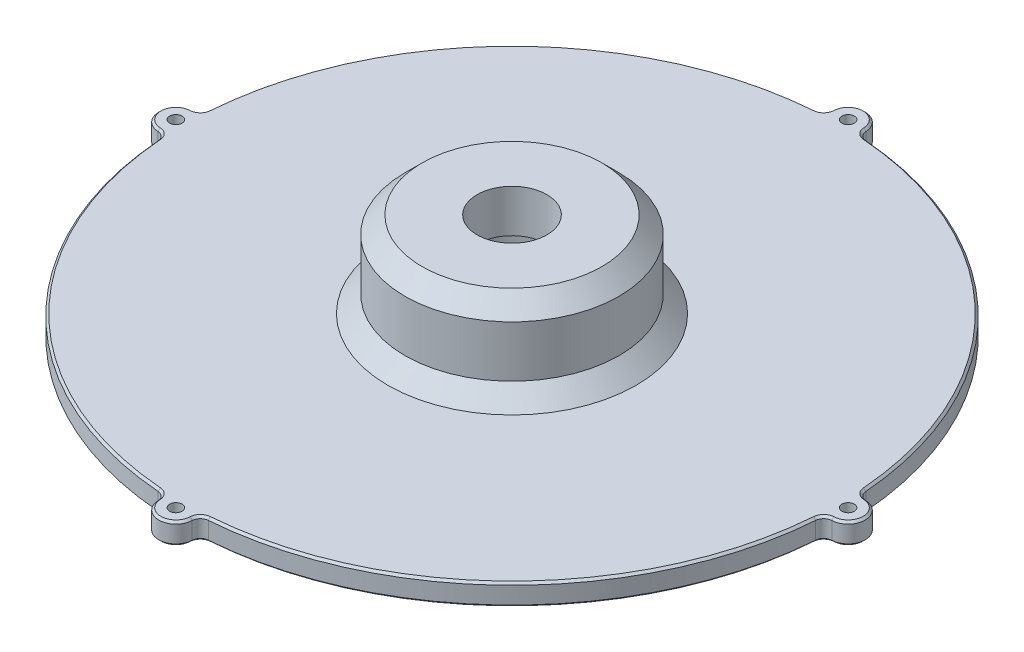
SolidWorks part; units mm, degrees
ref_plane "Płaszczyzna przednia" through (0, 0, 0) normal (0, 0, 1) x (1, 0, 0)
ref_plane "Płaszczyzna górna" through (0, 0, 0) normal (0, 1, 0) x (1, 0, 0)
ref_plane "Płaszczyzna prawa" through (0, 0, 0) normal (1, 0, 0) x (0, 0, -1)
sketch "Szkic2" plane through (0, 0, 0) normal (0, 0, 1) x (1, 0, 0)
  line L0 (15, 5) -> (15, 0)
  line L1 (15, 0) -> (77, 0)
  line L2 (77, 0) -> (77, 5)
  line L5 (77, 5) -> (15, 5)
  line L6 (0, 0) -> (0, 12.2819) construction
  line L7 (15, 5) -> (15, 15)
  line L8 (15, 15) -> (8.15, 15)
  line L9 (8.15, 15) -> (8.15, 25)
  line L10 (8.15, 25) -> (25, 25)
  line L11 (25, 25) -> (25, 5)
  dimension "D1" = 77
  dimension "D2" = 16.3
  dimension "D3" = 10
  dimension "D4" = 5
  dimension "D5" = 15
  dimension "D6" = 10
  dimension "D7" = 25
revolve "Obrót1" add sketch "Szkic2" angle 360 about L6 region at (46, 2.5, 0) region at (17.8506, 16.2756, 0)
sketch "Szkic3" plane through (0, 5, 0) normal (0, 1, 0) x (1, 0, 0)
  line L0 (0, 76) -> (0, 78.5) construction
  line L1 (-4, 76) -> (-4, 78.5)
  line L2 (4, 76) -> (4, 78.5)
  line L3 (76, 0) -> (78.5, 0) construction
  line L4 (76, 4) -> (78.5, 4)
  line L5 (76, -4) -> (78.5, -4)
  line L6 (0, -76) -> (0, -78.5) construction
  line L7 (4, -76) -> (4, -78.5)
  line L8 (-4, -76) -> (-4, -78.5)
  line L9 (-76, 0) -> (-78.5, 0) construction
  line L10 (-76, -4) -> (-78.5, -4)
  line L11 (-76, 4) -> (-78.5, 4)
  arc A1 (-4, 76) -> (4, 76) centre (0, 76) ccw
  arc A2 (4, 78.5) -> (-4, 78.5) centre (0, 78.5) ccw
  circle A3 centre (0, 78.5) radius 1.45
  circle A4 centre (78.5, 0) radius 1.45
  arc A5 (76, 4) -> (76, -4) centre (76, 0) ccw
  arc A6 (78.5, -4) -> (78.5, 4) centre (78.5, 0) ccw
  circle A7 centre (0, -78.5) radius 1.45
  arc A8 (4, -76) -> (-4, -76) centre (0, -76) ccw
  arc A9 (-4, -78.5) -> (4, -78.5) centre (0, -78.5) ccw
  circle A10 centre (-78.5, 0) radius 1.45
  arc A11 (-76, -4) -> (-76, 4) centre (-76, 0) ccw
  arc A12 (-78.5, 4) -> (-78.5, -4) centre (-78.5, 0) ccw
  point P6 (0, 77.25)
  point P18 (77.25, 0)
  point P27 (0, -77.25)
  point P36 (-77.25, 0)
  point P43 (0, 0)
  dimension "D1" = 2.9
  dimension "D2" = 4
  dimension "D3" = 2.5
  dimension "D5" = 78.5
  dimension "D4" = 4
extrude "Dodanie-wyciągnięcie1" add sketch "Szkic3" against normal blind 5 contours L11 A12 L10 A11 A10 | L8 A9 L7 A8 A7 | L5 A6 L4 A5 A4 | L2 A2 L1 A1 A3 region at (-3.868, 5, -77.25) region at (77.25, 5, -3.868) region at (3.868, 5, 77.25) region at (-77.25, 5, 3.868)
sketch "Szkic4" plane through (0, 5, 0) normal (0, 1, 0) x (1, 0, 0)
  line L1 (-12.5, 12.5) -> (12.5, 12.5) construction
  line L2 (-12.5, 12.5) -> (-12.5, -12.5) construction
  line L3 (-12.5, -12.5) -> (12.5, -12.5) construction
  line L4 (12.5, 12.5) -> (12.5, -12.5) construction
  line L5 (-12.5, 12.5) -> (12.5, -12.5) construction
  line L6 (-12.5, -12.5) -> (12.5, 12.5) construction
  circle A0 centre (12.5, 12.5) radius 3.1
  circle A1 centre (12.5, -12.5) radius 3.1
  circle A2 centre (-12.5, -12.5) radius 3.1
  circle A3 centre (-12.5, 12.5) radius 3.1
  point P0 (0, 0)
  dimension "D2" = 6.2
  dimension "D1" = 25
chamfer "Sfazowanie1" distance 4 angle 45 2 edges at (0, 5, -25) (0, 25, -25)
fillet "Zaokrąglenie1" radius 2 8 edges at (76.896, 2.5, 4) (76.896, 2.5, -4) (4, 2.5, 76.896) (-4, 2.5, 76.896) (-76.896, 2.5, 4) (-76.896, 2.5, -4) (4, 2.5, -76.896) (-4, 2.5, -76.896)
chamfer "Sfazowanie2" distance 0.5 angle 45 37 edges at (0, 0, -77.05) (78.5, 0, 1.45) (0, 0, 79.95) (-78.5, 0, 1.45) (0, 0, -15) (-82.5, 0, 0) (0, 0, 82.5) (82.5, 0, 0) (0, 0, -82.5) (-77.3798, 0, 4.5582) (-54.4472, 0, 54.4472) (-4.5582, 0, 77.3798) (4.5582, 0, 77.3798) (54.4472, 0, 54.4472) (77.3798, 0, 4.5582) (77.3798, 0, -4.5582) (54.4472, 0, -54.4472) (4.5582, 0, -77.3798) (-4.5582, 0, -77.3798) (-54.4472, 0, -54.4472) (-77.3798, 0, -4.5582) (54.4472, 5, -54.4472) (77.3798, 5, -4.5582) (4.5582, 5, -77.3798) (82.5, 5, 0) (0, 5, -82.5) (77.3798, 5, 4.5582) (-4.5582, 5, -77.3798) (54.4472, 5, 54.4472) (-54.4472, 5, -54.4472) (4.5582, 5, 77.3798) (-77.3798, 5, -4.5582) (0, 5, 82.5) (-82.5, 5, 0) (-4.5582, 5, 77.3798) (-77.3798, 5, 4.5582) (-54.4472, 5, 54.4472)
